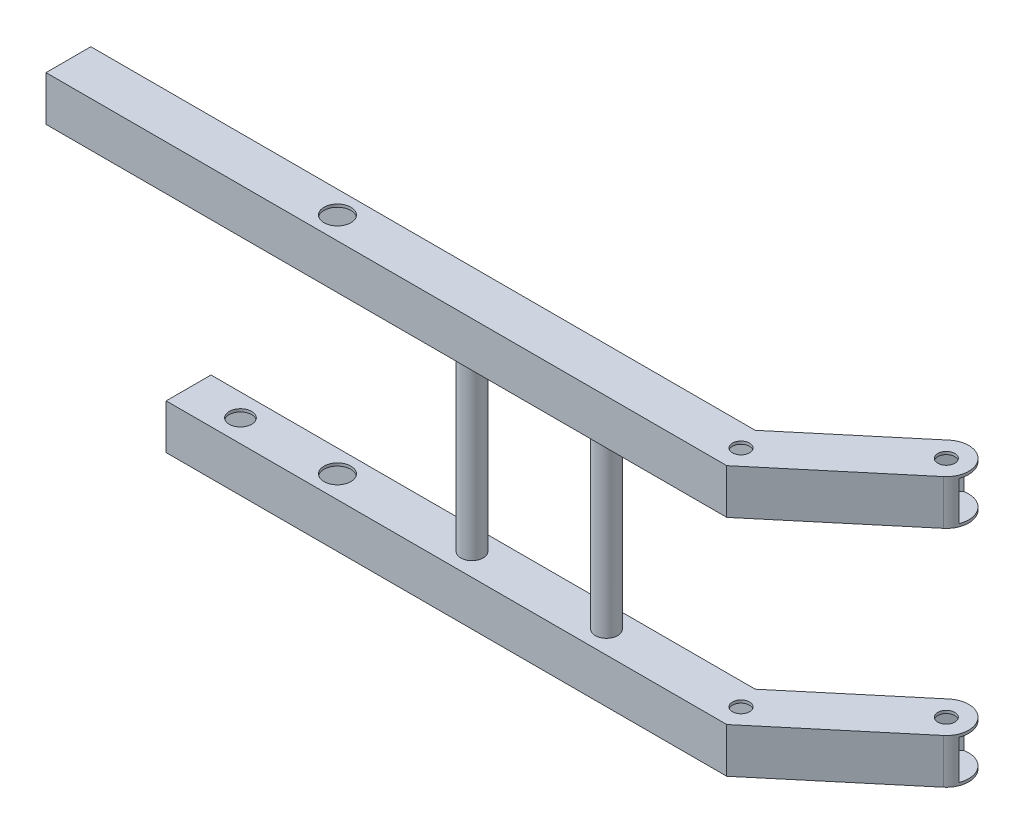
SolidWorks part; units mm, degrees
ref_plane "Front Plane" through (0, 0, 0) normal (0, 0, 1) x (1, 0, 0)
ref_plane "Top Plane" through (0, 0, 0) normal (0, 1, 0) x (1, 0, 0)
ref_plane "Right Plane" through (0, 0, 0) normal (1, 0, 0) x (0, 0, -1)
sketch "Sketch4" plane through (0, 0, 0) normal (0, 1, 0) x (1, 0, 0)
  line L0 (0, 0) -> (-254, 0) construction
  line L1 (0, 0) -> (91.1351, 76.4714) construction
  line L2 (-254, -12.7) -> (-254, 12.7)
  line L3 (4.6224, -12.7) -> (-4.6224, 12.7) construction
  line L4 (-254, 12.7) -> (-4.6224, 12.7)
  line L5 (99.2985, 66.7427) -> (82.9717, 86.2002)
  line L6 (82.9717, 86.2002) -> (-4.6224, 12.7)
  line L7 (-254, -12.7) -> (4.6224, -12.7)
  line L8 (4.6224, -12.7) -> (99.2985, 66.7427)
  circle A0 centre (0, 0) radius 4.826
  circle A1 centre (63.237, 53.0621) radius 4.826
  circle A3 centre (-228.6, 0) radius 7.62
  point P7 (-254, 0)
  point P10 (0, 0)
  point P13 (91.1351, 76.4714)
  dimension "D2" = 9.652
  dimension "D7" = 15.24
  dimension "D1" = 82.55
  dimension "D3" = 25.4
  dimension "D5" = 25.4
  dimension "D6" = 228.6
extrude "Boss-Extrude3" add sketch "Sketch4" along normal blind 152.4
sketch "Sketch5" plane through (-254, 0, 0) normal (-1, 0, 0) x (0, 0, 1)
  line L0 (0, 152.4) -> (0, 0) construction
  line L3 (-12.7, 152.4) -> (12.7, 152.4) construction
  line L6 (-12.7, 0) -> (12.7, 0) construction
  line L7 (11.1125, 128.5875) -> (-11.1125, 128.5875)
  line L8 (11.1125, 128.5875) -> (11.1125, 150.8125)
  line L9 (11.1125, 150.8125) -> (-11.1125, 150.8125)
  line L10 (-11.1125, 128.5875) -> (-11.1125, 150.8125)
  line L11 (11.1125, 128.5875) -> (-11.1125, 150.8125) construction
  line L12 (11.1125, 150.8125) -> (-11.1125, 128.5875) construction
  line L13 (-12.7, 127) -> (12.7, 127)
  line L14 (-12.7, 152.4) -> (-12.7, 0) construction
  line L15 (12.7, 152.4) -> (12.7, 0) construction
  line L16 (11.1125, 1.5875) -> (-11.1125, 1.5875)
  line L17 (11.1125, 1.5875) -> (11.1125, 23.8125)
  line L18 (11.1125, 23.8125) -> (-11.1125, 23.8125)
  line L19 (-11.1125, 1.5875) -> (-11.1125, 23.8125)
  line L20 (11.1125, 1.5875) -> (-11.1125, 23.8125) construction
  line L21 (11.1125, 23.8125) -> (-11.1125, 1.5875) construction
  line L22 (-12.7, 25.4) -> (12.7, 25.4)
  line L23 (-12.7, 25.4) -> (-12.7, 127)
  line L24 (12.7, 127) -> (12.7, 25.4)
  point P12 (0, 139.7)
  point P19 (0, 12.7)
  point P26 (0, 25.4)
  dimension "D1" = 1.5875
  dimension "D2" = 12.7
  dimension "D3" = 12.7
  dimension "D4" = 1.5875
  dimension "D5" = 12.7
  dimension "D6" = 12.7
extrude "Cut-Extrude2" cut sketch "Sketch5" against normal up to vertex (258.6224 mm away) up to point (4.6224, 152.4, 12.7)
sketch "Sketch6" plane through (91.1351, 0, -76.4714) normal (0.766, 0, -0.6428) x (-0.6428, 0, -0.766)
  line L0 (12.7, 127) -> (-12.7, 127)
  line L1 (12.7, 152.4) -> (12.7, 0) construction
  line L3 (0, 0) -> (0, 152.4) construction
  line L4 (-12.7, 0) -> (12.7, 0) construction
  line L5 (-12.7, 152.4) -> (12.7, 152.4) construction
  line L6 (-12.7, 152.4) -> (-12.7, 0) construction
  line L7 (-11.1125, 128.5875) -> (11.1125, 128.5875)
  line L8 (-11.1125, 128.5875) -> (-11.1125, 150.8125)
  line L9 (-11.1125, 150.8125) -> (11.1125, 150.8125)
  line L10 (11.1125, 128.5875) -> (11.1125, 150.8125)
  line L11 (-11.1125, 128.5875) -> (11.1125, 150.8125) construction
  line L12 (-11.1125, 150.8125) -> (11.1125, 128.5875) construction
  line L13 (12.7, 25.4) -> (-12.7, 25.4)
  line L14 (-11.1125, 1.5875) -> (11.1125, 1.5875)
  line L15 (-11.1125, 1.5875) -> (-11.1125, 23.8125)
  line L16 (-11.1125, 23.8125) -> (11.1125, 23.8125)
  line L17 (11.1125, 1.5875) -> (11.1125, 23.8125)
  line L18 (-11.1125, 1.5875) -> (11.1125, 23.8125) construction
  line L19 (-11.1125, 23.8125) -> (11.1125, 1.5875) construction
  line L20 (-12.7, 25.4) -> (-12.7, 127)
  line L21 (12.7, 127) -> (12.7, 25.4)
  point P5 (0, 127)
  point P12 (0, 139.7)
  point P18 (0, 25.4)
  point P19 (0, 12.7)
  dimension "D1" = 1.5875
  dimension "D2" = 12.7
  dimension "D3" = 12.7
  dimension "D4" = 1.5875
  dimension "D5" = 25.4
  dimension "D6" = 12.7
extrude "Cut-Extrude3" cut sketch "Sketch6" against normal up to vertex (123.5909 mm away) up to point (4.6224, 152.4, 12.7)
sketch "Sketch7" plane through (0, 152.4, 0) normal (0, 1, 0) x (1, 0, 0)
  line L0 (71.4004, 43.3334) -> (55.0736, 62.7909) construction
  line L1 (82.9717, 86.2002) -> (-4.6224, 12.7) construction
  line L2 (4.6224, -12.7) -> (99.2985, 66.7427) construction
  line L3 (55.0736, 62.7909) -> (14.2925, 190.3795)
  line L4 (14.2925, 190.3795) -> (153.8443, 116.5917)
  line L5 (153.8443, 116.5917) -> (141.5355, -3.4731)
  line L6 (141.5355, -3.4731) -> (71.4004, 43.3334)
  arc A0 (55.0736, 62.7909) -> (71.4004, 43.3334) centre (63.237, 53.0621) cw
  point P6 (63.237, 53.0621)
  point P7 (63.237, 53.0621)
extrude "Cut-Extrude4" cut sketch "Sketch7" against normal up to surface (152.4 mm away) up to face at (-54.2883, 0, -25.4905)
sketch "Sketch8" plane through (0, 127, 0) normal (0, -1, 0) x (1, 0, 0)
  line L0 (0, 0) -> (-228.6, 0) construction
  circle A0 centre (-76.2, 0) radius 6.35
  circle A1 centre (-152.4, 0) radius 6.35
  dimension "D3" = 12.7
  dimension "D1" = 76.2
  dimension "D2" = 76.2
extrude "Boss-Extrude4" add sketch "Sketch8" along normal up to surface (101.6 mm away) up to face at (-61.9662, 25.4, -19.0479)
sketch "Sketch9" plane through (-254, 0, 0) normal (-1, 0, 0) x (0, 0, 1)
  line L0 (-12.7, 152.4) -> (12.7, 152.4)
  line L1 (12.7, 152.4) -> (12.7, 127)
  line L2 (12.7, 127) -> (-12.7, 127)
  line L3 (-12.7, 152.4) -> (-12.7, 127) construction
  line L4 (12.7, 127) -> (-12.7, 127) construction
  line L5 (-12.7, 127) -> (-12.7, 152.4)
  line L6 (-11.1125, 150.8125) -> (11.1125, 150.8125)
  line L7 (11.1125, 150.8125) -> (11.1125, 128.5875)
  line L8 (11.1125, 128.5875) -> (-11.1125, 128.5875)
  line L9 (-11.1125, 128.5875) -> (-11.1125, 150.8125)
  line L10 (-12.7, 25.4) -> (12.7, 25.4)
  line L11 (12.7, 25.4) -> (12.7, 0)
  line L12 (12.7, 0) -> (-12.7, 0)
  line L13 (-12.7, 0) -> (-12.7, 25.4)
  line L14 (-11.1125, 23.8125) -> (11.1125, 23.8125)
  line L15 (11.1125, 23.8125) -> (11.1125, 1.5875)
  line L16 (11.1125, 1.5875) -> (-11.1125, 1.5875)
  line L17 (-11.1125, 1.5875) -> (-11.1125, 23.8125)
extrude "Boss-Extrude5" add sketch "Sketch9" along normal blind 58.928
sketch "Sketch11" plane through (0, 127, 0) normal (0, -1, 0) x (1, 0, 0)
  line L0 (-312.928, 0) -> (-228.6, 0) construction
  line L1 (-312.928, -12.7) -> (-312.928, 12.7) construction
  circle A0 centre (-271.0548, 0) radius 1.65
  circle A1 centre (-296.0548, 0) radius 1.65
  dimension "D2" = 3.3
  dimension "D1" = 25
extrude "Cut-Extrude6" cut sketch "Sketch11" against normal up to surface (1.5875 mm away) up to face at (0, 128.5875, -4.826)
sketch "Sketch12" plane through (0, 127, 0) normal (0, -1, 0) x (1, 0, 0)
  line L0 (-271.0548, 0) -> (-296.0548, 0) construction
  circle A0 centre (-283.5548, 0) radius 6.35
extrude "Cut-Extrude7" cut sketch "Sketch12" along normal up to surface (103.1875 mm away) up to face at (-228.6, 23.8125, 7.62)
sketch "Sketch13" plane through (-312.928, 0, 0) normal (-1, 0, 0) x (0, 0, 1)
  line L1 (12.7, 152.4) -> (-12.7, 152.4)
  line L2 (12.7, 152.4) -> (12.7, 127)
  line L3 (12.7, 127) -> (-12.7, 127)
  line L4 (-12.7, 152.4) -> (-12.7, 127)
  line L5 (-11.1125, 128.5875) -> (11.1125, 128.5875)
  line L6 (-11.1125, 128.5875) -> (-11.1125, 150.8125)
  line L7 (-11.1125, 150.8125) -> (11.1125, 150.8125)
  line L8 (11.1125, 128.5875) -> (11.1125, 150.8125)
extrude "Boss-Extrude6" add sketch "Sketch13" along normal blind 68.072
